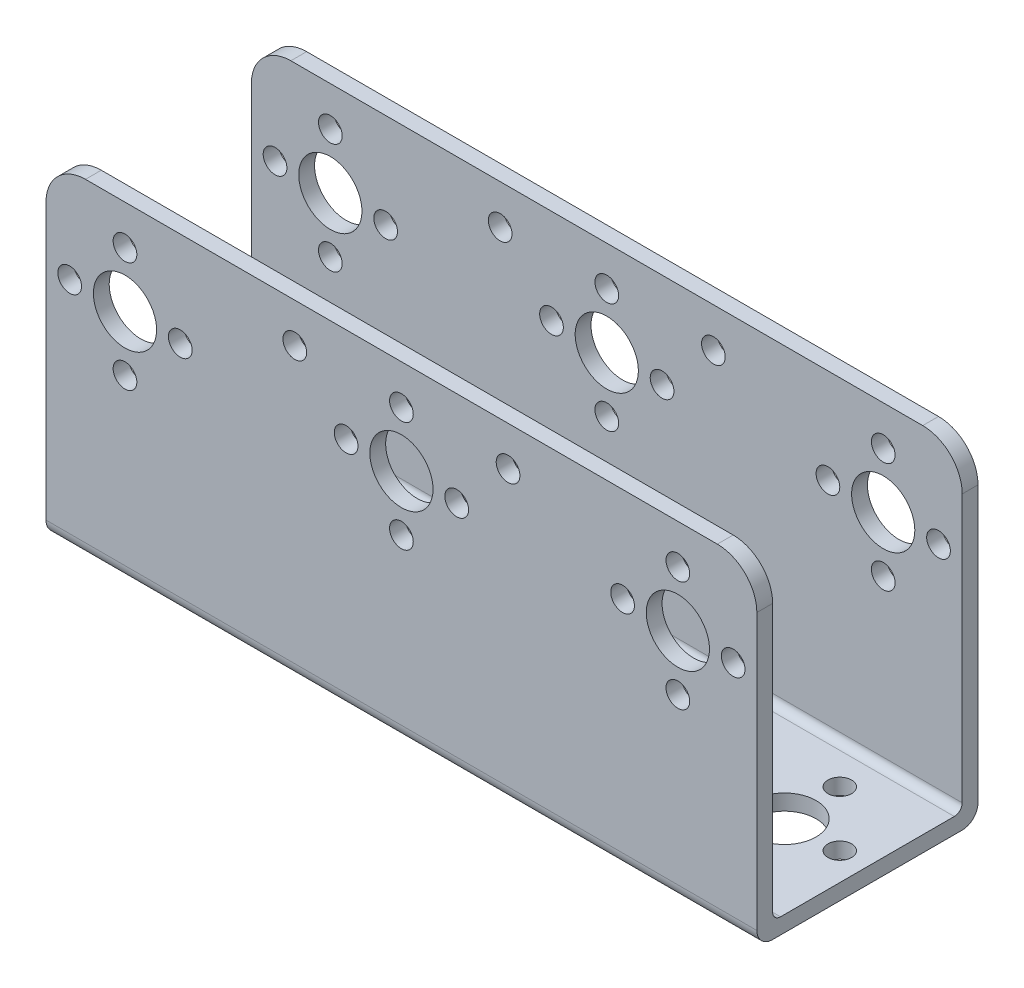
SolidWorks part; units mm, degrees
ref_plane "Piano frontale" through (0, 0, 0) normal (0, 0, 1) x (1, 0, 0)
ref_plane "Piano superiore" through (0, 0, 0) normal (0, 1, 0) x (1, 0, 0)
ref_plane "Piano destro" through (0, 0, 0) normal (1, 0, 0) x (0, 0, -1)
sketch "Schizzo1" plane through (0, 0, 0) normal (0, 0, 1) x (1, 0, 0)
  line L1 (0, 0) -> (90, 0)
  line L2 (0, 0) -> (0, 36.8605)
  line L3 (5, 41.8605) -> (85, 41.8605)
  line L4 (90, 0) -> (90, 36.8605)
  arc A0 (85, 41.8605) -> (90, 36.8605) centre (85, 36.8605) cw
  arc A1 (0, 36.8605) -> (5, 41.8605) centre (5, 36.8605) cw
  point P7 (90, 41.8605)
  point P10 (0, 41.8605)
  dimension "D3" = 5
  dimension "D1" = 90
  dimension "D2" = 41.8605
extrude "Estrusione-Estrusione1" add sketch "Schizzo1" against normal blind 2
sketch "Schizzo2" plane through (0, 0, 0) normal (0, 1, 0) x (1, 0, 0)
  line L1 (0, 0) -> (90, 0)
  line L2 (0, 0) -> (0, 28)
  line L3 (0, 28) -> (90, 28)
  line L4 (90, 0) -> (90, 28)
  dimension "D1" = 90
  dimension "D2" = 28
extrude "Estrusione-Estrusione2" add sketch "Schizzo2" along normal blind 2
ref_plane "Piano1" through (0, 0, -28) normal (0, 0, 1) x (1, 0, 0)
sketch "Schizzo4" plane through (0, 0, -28) normal (0, 0, 1) x (1, 0, 0)
  line L4 (90, 0) -> (90, 36.8605)
  line L5 (85, 41.8605) -> (5, 41.8605)
  line L6 (0, 36.8605) -> (0, 0)
  line L7 (0, 0) -> (90, 0)
  line L8 (90, 0) -> (90, 36.8605)
  line L9 (85, 41.8605) -> (5, 41.8605)
  line L10 (0, 36.8605) -> (0, 0)
  line L11 (0, 0) -> (90, 0)
  arc A2 (90, 36.8605) -> (85, 41.8605) centre (85, 36.8605) ccw
  arc A3 (5, 41.8605) -> (0, 36.8605) centre (5, 36.8605) ccw
  arc A4 (90, 36.8605) -> (85, 41.8605) centre (85, 36.8605) ccw
  arc A5 (5, 41.8605) -> (0, 36.8605) centre (5, 36.8605) ccw
  dimension "D1" = 0
extrude "Estrusione-Estrusione3" add sketch "Schizzo4" along normal blind 2
sketch "Schizzo5" plane through (0, 0, 0) normal (0, 0, 1) x (1, 0, 0)
  line L0 (10, 22.8605) -> (45, 22.8605) construction
  line L1 (85, 41.8605) -> (5, 41.8605) construction
  line L2 (0, 36.8605) -> (0, 0) construction
  line L3 (10, 29.8605) -> (45, 29.8605) construction
  line L4 (90, 0) -> (90, 36.8605) construction
  line L5 (45, 29.8605) -> (80, 29.8605) construction
  line L6 (45, 22.8605) -> (80, 22.8605) construction
  line L7 (10, 36.8605) -> (45, 36.8605) construction
  line L8 (45, 36.8605) -> (80, 36.8605) construction
  circle A0 centre (10, 29.8605) radius 4
  circle A1 centre (45, 29.8605) radius 4
  circle A2 centre (80, 29.8605) radius 4
  circle A3 centre (10, 36.8605) radius 1.5
  circle A4 centre (3, 29.8605) radius 1.5
  circle A5 centre (10, 22.8605) radius 1.5
  circle A6 centre (17, 29.8605) radius 1.5
  circle A7 centre (38, 29.8605) radius 1.5
  circle A8 centre (45, 36.8605) radius 1.5
  circle A9 centre (80, 36.8605) radius 1.5
  circle A10 centre (73, 29.8605) radius 1.5
  circle A11 centre (45, 22.8605) radius 1.5
  circle A12 centre (80, 22.8605) radius 1.5
  circle A13 centre (87, 29.8605) radius 1.5
  circle A16 centre (52, 29.8605) radius 1.5
  point P6 (0, 0)
  point P7 (0, 0)
  point P8 (0, 0)
  point P9 (0, 0)
  point P14 (0, 0)
  point P15 (0, 0)
  point P42 (0, 0)
  dimension "D1" = 8
  dimension "D2" = 7
  dimension "D3" = 7
  dimension "D4" = 7
  dimension "D5" = 3
  dimension "D6" = 7
  dimension "D7" = 7
  dimension "D8" = 7
  dimension "D9" = 7
  dimension "D10" = 7
  dimension "D11" = 7
  dimension "D12" = 7
  dimension "D13" = 7
  dimension "D14" = 7
  dimension "D15" = 12
  dimension "D16" = 10
  dimension "D17" = 10
  dimension "D18" = 3
  dimension "D19" = 3
extrude "Taglio-Estrusione1" cut sketch "Schizzo5" against normal through all
fillet "Raccordo1" radius 2 1 edges at (45, 0, -28)
fillet "Raccordo2" radius 2 1 edges at (45, 0, 0)
fillet "Raccordo3" radius 1 1 edges at (45, 2, -2)
fillet "Raccordo4" radius 1 1 edges at (45, 2, -26)
sketch "Schizzo6" plane through (0, 0, 0) normal (0, 1, 0) x (1, 0, 0)
  line L0 (0, 14) -> (90, 14) construction
  line L1 (0, 25) -> (0, 3) construction
  line L2 (90, 3) -> (90, 25) construction
  line L3 (10.5, 3) -> (10.5, 14) construction
  line L4 (0, 3) -> (90, 3) construction
  line L5 (10.5, 14) -> (10.5, 25) construction
  line L6 (90, 25) -> (0, 25) construction
  line L7 (45, 3) -> (45, 14) construction
  line L8 (45, 14) -> (45, 25) construction
  line L9 (79.5, 3) -> (79.5, 14) construction
  line L10 (79.5, 14) -> (79.5, 25) construction
  circle A0 centre (45, 14) radius 4
  circle A1 centre (10.5, 14) radius 4
  circle A2 centre (79.5, 14) radius 4
  circle A3 centre (10.5, 21) radius 1.5
  circle A4 centre (3.5, 14) radius 1.5
  circle A5 centre (10.5, 7) radius 1.5
  circle A6 centre (17.5, 14) radius 1.5
  circle A7 centre (38, 14) radius 1.5
  circle A8 centre (45, 21) radius 1.5
  circle A9 centre (79.5, 21) radius 1.5
  circle A10 centre (79.5, 7) radius 1.5
  circle A11 centre (45, 7) radius 1.5
  circle A12 centre (52, 14) radius 1.5
  circle A13 centre (86.5, 14) radius 1.5
  circle A14 centre (72.5, 14) radius 1.5
  dimension "D1" = 8
  dimension "D4" = 3
  dimension "D2" = 10.5
  dimension "D3" = 10.5
  dimension "D5" = 7
  dimension "D6" = 7
  dimension "D7" = 7
  dimension "D8" = 7
  dimension "D9" = 7
  dimension "D10" = 7
  dimension "D11" = 7
  dimension "D12" = 7
  dimension "D13" = 7
  dimension "D14" = 7
  dimension "D15" = 7
  dimension "D16" = 7
extrude "Taglio-Estrusione2" cut sketch "Schizzo6" along normal through all
sketch "Sketch1" plane through (0, 0, 0) normal (0, 0, 1) x (1, 0, 0)
  line L0 (85, 41.8605) -> (5, 41.8605) construction
  line L1 (45, 36.8605) -> (45, 41.8605) construction
  line L2 (45, 36.8605) -> (45, 22.8605) construction
  circle A0 centre (31.5, 36.8605) radius 1.5
  circle A1 centre (58.5, 36.8605) radius 1.5
  dimension "D1" = 3
  dimension "D2" = 3
  dimension "D3" = 5
  dimension "D4" = 5
  dimension "D5" = 13.5
  dimension "D6" = 13.5
extrude "Cut-Extrude1" cut sketch "Sketch1" against normal through all both and the other way through all
